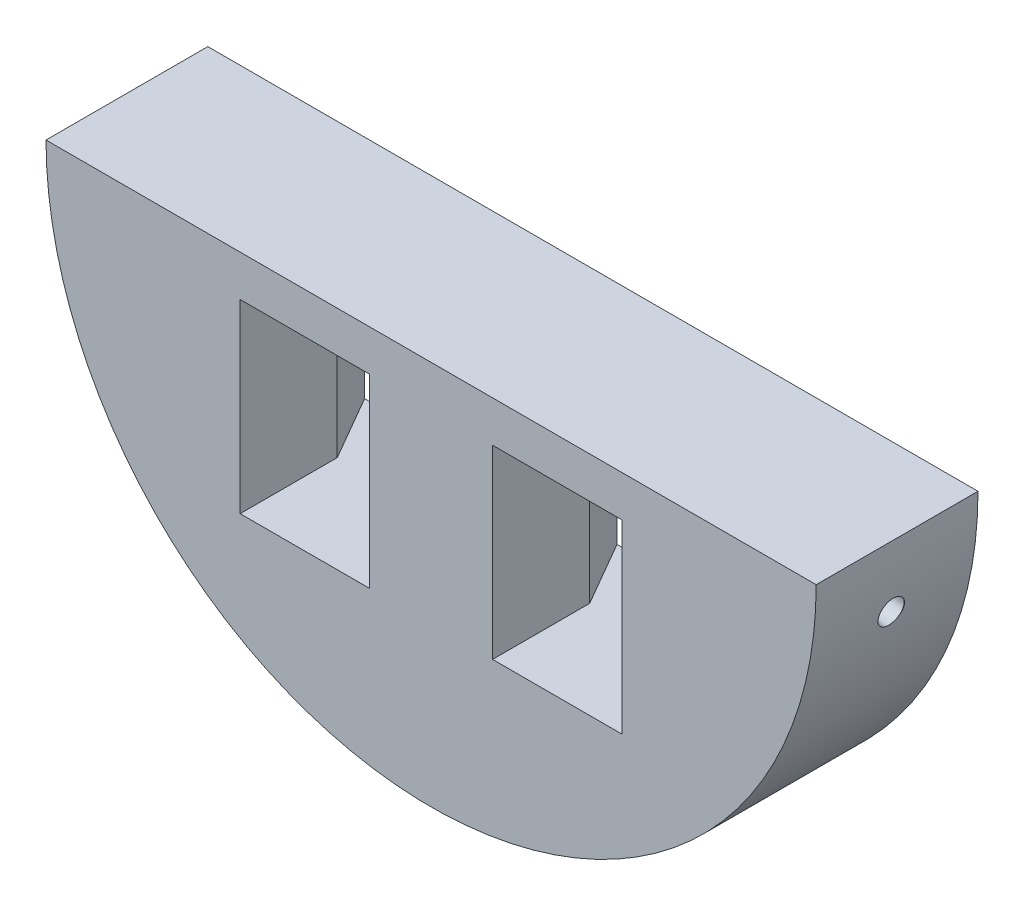
SolidWorks part; units mm, degrees
ref_plane "Front Plane" through (0, 0, 0) normal (0, 0, 1) x (1, 0, 0)
ref_plane "Top Plane" through (0, 0, 0) normal (0, 1, 0) x (1, 0, 0)
ref_plane "Right Plane" through (0, 0, 0) normal (1, 0, 0) x (0, 0, -1)
sketch "Sketch1" plane through (0, 0, 0) normal (0, 0, 1) x (1, 0, 0)
  line L0 (-119, 0) -> (0, 0)
  line L3 (-50, -35) -> (-30, -35)
  line L4 (-50, -35) -> (-50, -15)
  line L5 (-50, -15) -> (-30, -15)
  line L6 (-30, -35) -> (-30, -15)
  line L7 (-89, -35) -> (-69, -35)
  line L8 (-89, -35) -> (-89, -15)
  line L9 (-89, -15) -> (-69, -15)
  line L10 (-69, -35) -> (-69, -15)
  arc A1 (-119, 0) -> (0, 0) centre (-59.5, 0) ccw
  dimension "D1" = 30
  dimension "D7" = 59.5
  dimension "D2" = 15
  dimension "D3" = 30
  dimension "D4" = 20
extrude "Boss-Extrude1" add sketch "Sketch1" along normal blind 25
hole_wizard "Ø4.0mm Dowel Hole2" positions "3DSketch2" profile "Sketch4" hole size "Ø4.0" standard "ANSI Metric"
sketch3d "3DSketch2"
  line L2 (0, 0, 25) -> (0, 0, 0) construction
  line L4 (0, 0, 25) -> (0, 0, 0) construction
  line L5 (0, 0, 12.5) -> (-0.9039, -10.3321, 12.5) construction
  line L8 (-59.5, 0, 0) -> (-59.5, 0, 25) construction
  line L9 (0, 0, 0) -> (-119, 0, 0) construction
  line L10 (0, 0, 25) -> (-119, 0, 25) construction
  line L12 (-59.5, 0, 12.5) -> (-0.9039, -10.3321, 12.5) construction
  line L16 (-59.5, 0, 12.5) -> (0, 0, 12.5) construction
  point P0 (-0.9039, -10.3321, 12.5)
  point P16 (-0.9039, -10.3321, 12.5)
  point P23 (-0.9039, -10.3321, 12.5)
  point P25 (-0.9039, -10.3321, 12.5)
  dimension "D1" = 10
sketch "Sketch4" plane through (-0.9039, -10.3321, 12.5) normal (0, 0, 1) x (0.1736, 0.9848, 0)
  line L0 (0, 0) -> (0, 11.2017)
  line L1 (0, 11.2017) -> (2, 10)
  line L2 (2, 10) -> (2, 0.025)
  line L3 (2, 0.025) -> (2.025, 0)
  line L5 (2.025, 0) -> (0, 0)
  line L6 (-2, 0.025) -> (-2.025, 0) construction
  line L10 (0, 11.2017) -> (-2, 10) construction
  line L11 (0, -6.35) -> (0, 107.95) construction
  dimension "Hole Dia." = 4
  dimension "Hole Depth" = 10
  dimension "Near C'Sink Dia." = 4.05
  dimension "Near C'Sink Angle" = 90
  dimension "Drill Angle" = 118
pattern_circular "CirPattern1" count 5 over 160 about axis through (-59.5, 0, 0) along (0, 0, 1) of "Ø4.0mm Dowel Hole2" reverse direction yes
chamfer "Chamfer1" distance 15 angle 30 2 edges at (-79, -15, 25) (-40, -15, 25) first distance on face at (-79, -15, 12.5) first distance on face at (-40, -15, 12.5)
chamfer "Chamfer2" distance 10 angle 30 4 edges at (-50, -25, 0) (-30, -25, 0) (-89, -25, 0) (-69, -25, 0) first distance on face at (-50, -21.2679, 12) first distance on face at (-30, -21.2679, 12) first distance on face at (-89, -21.2679, 12) first distance on face at (-69, -21.2679, 12)
